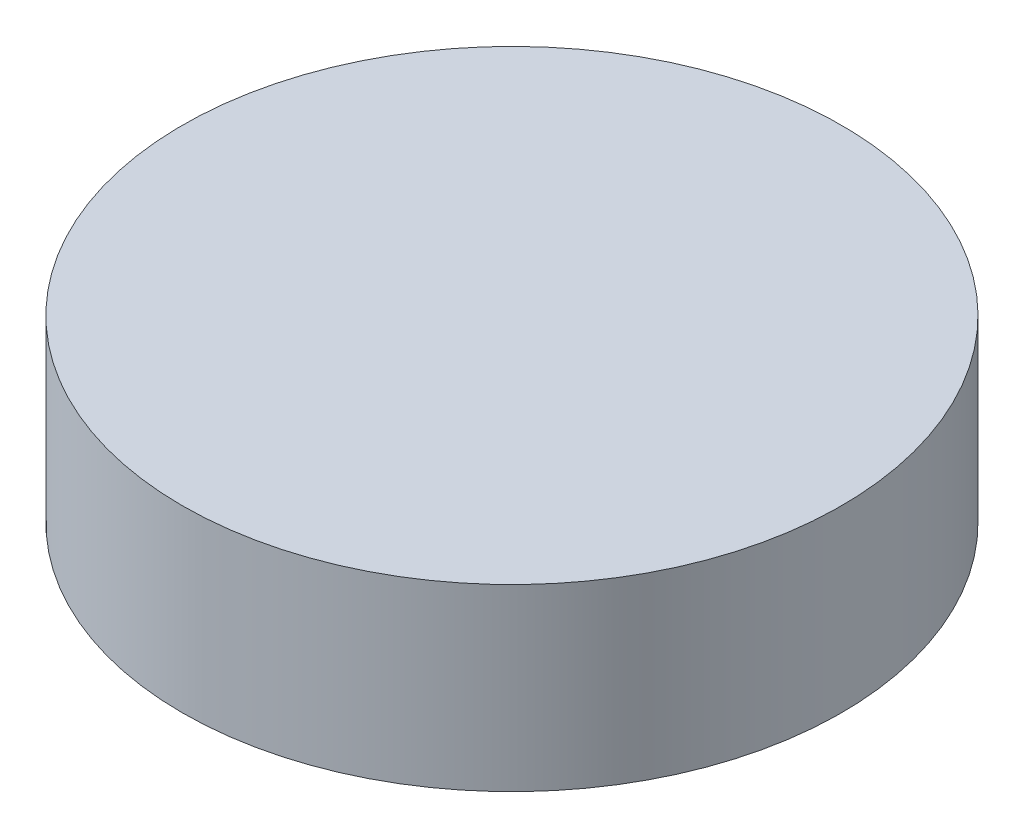
SolidWorks part; units mm, degrees
ref_plane "Front Plane" through (0, 0, 0) normal (0, 0, 1) x (1, 0, 0)
ref_plane "Top Plane" through (0, 0, 0) normal (0, 1, 0) x (1, 0, 0)
ref_plane "Right Plane" through (0, 0, 0) normal (1, 0, 0) x (0, 0, -1)
sketch "Sketch1" plane through (0, 0, 0) normal (0, 1, 0) x (1, 0, 0)
  circle A0 centre (0, 0) radius 18.375
  dimension "D1" = 36.75
extrude "Boss-Extrude1" add sketch "Sketch1" along normal blind 10
